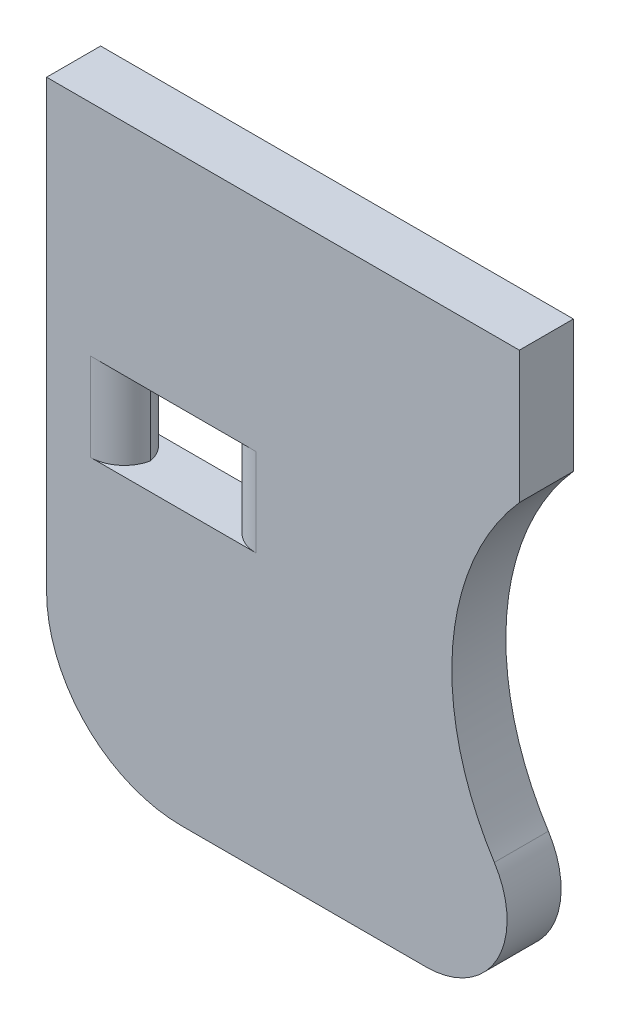
SolidWorks part; units mm, degrees
ref_plane "Plan de face" through (0, 0, 0) normal (0, 0, 1) x (1, 0, 0)
ref_plane "Plan de dessus" through (0, 0, 0) normal (0, 1, 0) x (1, 0, 0)
ref_plane "Plan de droite" through (0, 0, 0) normal (1, 0, 0) x (0, 0, -1)
sketch "Esquisse1" plane through (0, 0, 0) normal (0, 0, 1) x (1, 0, 0)
  line L0 (-34.4441, -52.025) -> (-34.4441, -52.525)
  line L1 (-80, -9.525) -> (-45, -9.525)
  line L2 (-80, -9.525) -> (-80, -42.525)
  line L3 (-70, -52.525) -> (-34.4441, -52.525)
  line L4 (-45, -9.525) -> (-45, -19.2962)
  arc A0 (-70, -52.525) -> (-80, -42.525) centre (-70, -42.525) cw
  arc A1 (-45, -19.2962) -> (-34.4441, -52.025) centre (-30, -32.525) ccw
  point P10 (-80, -52.525)
  dimension "D4" = 40
  dimension "D6" = 10
  dimension "D1" = 43
  dimension "D2" = 35
  dimension "D3" = 15
  dimension "D5" = 20
  dimension "D7" = 0.5
extrude "Boss.-Extru.1" add sketch "Esquisse1" along normal blind 4 contours L3 L0 A1 L4 L1 L2 A0
sketch "Esquisse2" plane through (0, 0, 0) normal (0, 0, -1) x (-1, 0, 0)
  line L1 (67, -25.775) -> (74.25, -25.775)
  line L2 (67, -25.775) -> (67, -32.275)
  line L3 (67, -32.275) -> (74.25, -32.275)
  line L4 (74.25, -25.775) -> (74.25, -32.275)
  line L5 (67, -25.775) -> (74.25, -32.275) construction
  line L6 (67, -32.275) -> (74.25, -25.775) construction
  line L7 (45, -9.525) -> (45, -19.2962) construction
  line L9 (81.4466, -26.025) -> (56.3197, -26.025) construction
  point P0 (70.625, -29.025)
  dimension "D1" = 22
  dimension "D2" = 7.25
  dimension "D3" = 6.5
  dimension "D4" = 0.25
extrude "Enlèv. mat.-Extru.1" cut sketch "Esquisse2" against normal through all
fillet "Congé1" radius 2.5 4 edges at (-74.25, -29.025, 4) (-67, -29.025, 4) (-74.25, -29.025, 0) (-67, -29.025, 0)
sketch "Sketch1" plane through (0, 0, 0) normal (0, 0, -1) x (-1, 0, 0)
  line L0 (70, -52.525) -> (34.4441, -52.525) construction
  line L1 (51.9089, -52.525) -> (34.4441, -52.525)
  line L2 (34.4441, -52.525) -> (34.4441, -52.025)
  line L3 (46.853, -43.2942) -> (34.4441, -52.025)
  arc A0 (51.9089, -52.525) -> (46.853, -43.2942) centre (51.9089, -46.525) cw
  arc A1 (34.4441, -52.025) -> (45, -19.2962) centre (30, -32.525) ccw construction
  dimension "D1" = 6
extrude "Cut-Extrude1" cut sketch "Sketch1" against normal up to next
